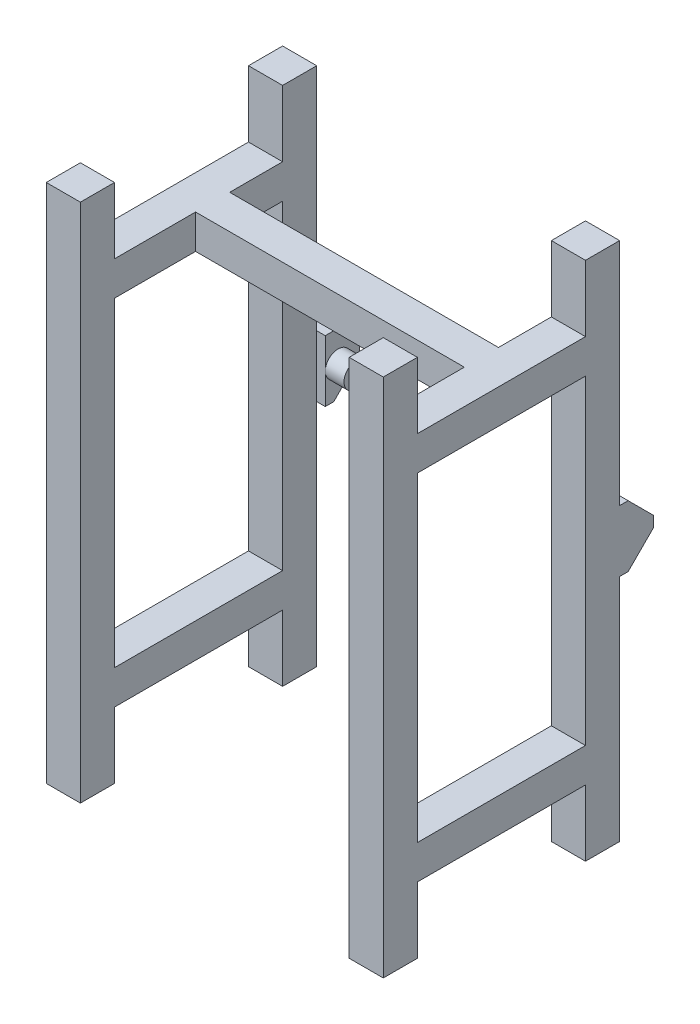
SolidWorks part; units mm, degrees
ref_plane "Front Plane" through (0, 0, 0) normal (0, 0, 1) x (1, 0, 0)
ref_plane "Top Plane" through (0, 0, 0) normal (0, 1, 0) x (1, 0, 0)
ref_plane "Right Plane" through (0, 0, 0) normal (1, 0, 0) x (0, 0, -1)
sketch "Sketch1" plane through (0, 0, 0) normal (0, 1, 0) x (1, 0, 0)
  line L0 (0, 98.5) -> (0, -98.5) construction
  line L1 (-157.5, -98.5) -> (157.5, -98.5) construction
  line L2 (-157.5, -98.5) -> (-157.5, 98.5) construction
  line L3 (-157.5, 98.5) -> (157.5, 98.5) construction
  line L4 (157.5, -98.5) -> (157.5, 98.5) construction
  line L5 (-157.5, -98.5) -> (157.5, 98.5) construction
  line L6 (-157.5, 98.5) -> (157.5, -98.5) construction
  line L7 (-157.5, 98.5) -> (-197.5, 98.5)
  line L8 (-157.5, 98.5) -> (-157.5, 138.5)
  line L9 (-157.5, 138.5) -> (-197.5, 138.5)
  line L10 (-197.5, 98.5) -> (-197.5, 138.5)
  line L11 (-157.5, 0) -> (157.5, 0) construction
  line L12 (157.5, 138.5) -> (197.5, 138.5)
  line L13 (197.5, 98.5) -> (197.5, 138.5)
  line L14 (157.5, 98.5) -> (197.5, 98.5)
  line L15 (157.5, 98.5) -> (157.5, 138.5)
  line L16 (157.5, -98.5) -> (157.5, -138.5)
  line L17 (157.5, -98.5) -> (197.5, -98.5)
  line L18 (197.5, -98.5) -> (197.5, -138.5)
  line L19 (157.5, -138.5) -> (197.5, -138.5)
  line L20 (-157.5, -138.5) -> (-197.5, -138.5)
  line L21 (-197.5, -98.5) -> (-197.5, -138.5)
  line L22 (-157.5, -98.5) -> (-197.5, -98.5)
  line L23 (-157.5, -98.5) -> (-157.5, -138.5)
  point P0 (0, 0)
  dimension "D1" = 40
  dimension "D2" = 40
  dimension "D3" = 197
  dimension "D4" = 315
extrude "Boss-Extrude1" add sketch "Sketch1" along normal blind 610
sketch "Sketch2" plane through (0, 0, 98.5) normal (0, 0, -1) x (-1, 0, 0)
  line L0 (157.5, 610) -> (157.5, 0) construction
  line L1 (157.5, 77.5) -> (197.5, 77.5)
  line L2 (157.5, 77.5) -> (157.5, 117.5)
  line L3 (157.5, 117.5) -> (197.5, 117.5)
  line L4 (197.5, 77.5) -> (197.5, 117.5)
  line L5 (197.5, 610) -> (197.5, 0) construction
  line L6 (0, 0) -> (0, 609.4131) construction
  line L7 (197.5, 305) -> (-198.2487, 305) construction
  line L8 (-157.5, 117.5) -> (-197.5, 117.5)
  line L9 (-197.5, 77.5) -> (-197.5, 117.5)
  line L10 (-157.5, 77.5) -> (-197.5, 77.5)
  line L11 (-157.5, 77.5) -> (-157.5, 117.5)
  line L12 (-157.5, 532.5) -> (-157.5, 492.5)
  line L13 (-157.5, 532.5) -> (-197.5, 532.5)
  line L14 (-197.5, 532.5) -> (-197.5, 492.5)
  line L15 (-157.5, 492.5) -> (-197.5, 492.5)
  line L16 (157.5, 492.5) -> (197.5, 492.5)
  line L17 (197.5, 532.5) -> (197.5, 492.5)
  line L18 (157.5, 532.5) -> (197.5, 532.5)
  line L19 (157.5, 532.5) -> (157.5, 492.5)
  point P25 (177.5, 117.5)
  dimension "D1" = 375
  dimension "D2" = 40
extrude "Boss-Extrude2" add sketch "Sketch2" along normal up to next (197 mm away)
sketch "Sketch3" plane through (-157.5, 0, 0) normal (1, 0, 0) x (0, 0, -1)
  line L0 (98.5, 532.5) -> (-98.5, 532.5) construction
  line L1 (-3.5, 532.5) -> (36.5, 532.5)
  line L2 (-3.5, 532.5) -> (-3.5, 492.5)
  line L3 (-3.5, 492.5) -> (36.5, 492.5)
  line L4 (36.5, 532.5) -> (36.5, 492.5)
  line L5 (98.5, 492.5) -> (-98.5, 492.5) construction
  line L6 (-98.5, 610) -> (-98.5, 532.5) construction
  dimension "D1" = 40
  dimension "D2" = 95
extrude "Boss-Extrude3" add sketch "Sketch3" along normal up to next
sketch "Sketch4" plane through (0, 0, -138.5) normal (0, 0, -1) x (-1, 0, 0)
  line L0 (197.5, 610) -> (197.5, 0) construction
  line L1 (197.5, 269) -> (147.5, 269)
  line L2 (197.5, 269) -> (197.5, 341)
  line L3 (197.5, 341) -> (147.5, 341)
  line L4 (147.5, 269) -> (147.5, 341)
  point P6 (197.5, 305)
  point P7 (197.5, 305)
  dimension "D1" = 50
  dimension "D2" = 72
extrude "Boss-Extrude4" add sketch "Sketch4" along normal blind 40
chamfer "Chamfer1" distance 30 2 edges at (-172.5, 269, -178.5) (-172.5, 341, -178.5)
sketch "Sketch5" plane through (-147.5, 0, 0) normal (1, 0, 0) x (0, 0, -1)
  line L0 (138.5, 305) -> (178.5, 305) construction
  line L1 (138.5, 341) -> (138.5, 269) construction
  line L2 (178.5, 311) -> (178.5, 299) construction
  circle A0 centre (153.5, 305) radius 15
  dimension "D1" = 30
extrude "Boss-Extrude5" add sketch "Sketch5" along normal blind 22 contours A0
ref_plane "Plane1" through (0, 0, 0) normal (1, 0, 0) x (0, 0, -1)
mirror "Mirror1" about plane through (0, 0, 0) normal (1, 0, 0) of "Boss-Extrude5", "Chamfer1", "Boss-Extrude4"
